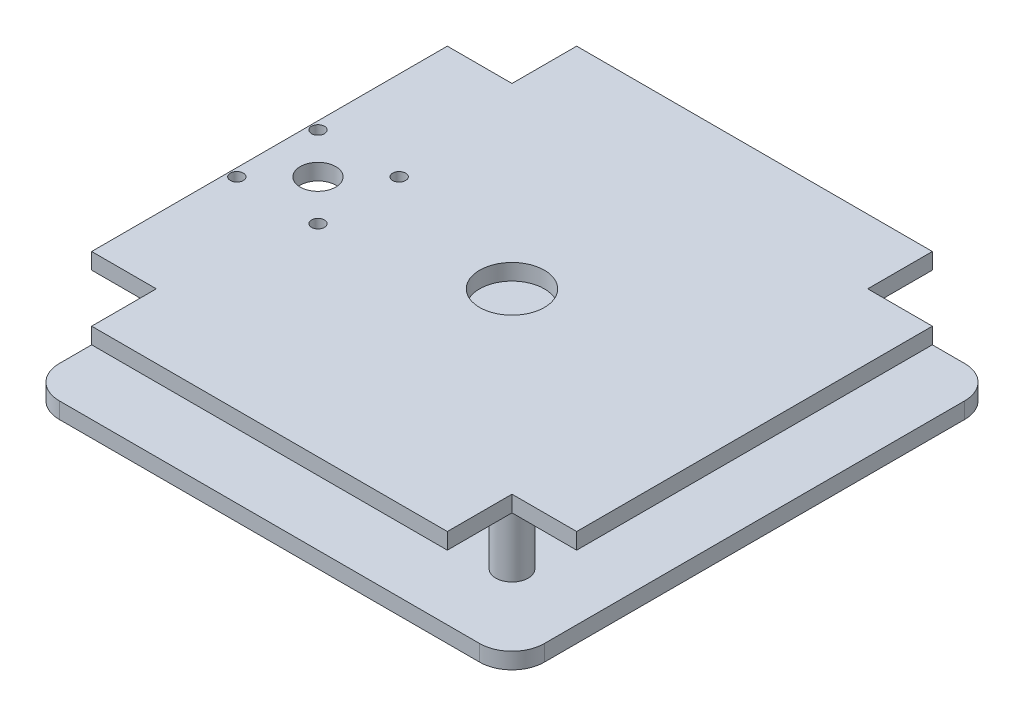
SolidWorks part; units mm, degrees
ref_plane "Front Plane" through (0, 0, 0) normal (0, 0, 1) x (1, 0, 0)
ref_plane "Top Plane" through (0, 0, 0) normal (0, 1, 0) x (1, 0, 0)
ref_plane "Right Plane" through (0, 0, 0) normal (1, 0, 0) x (0, 0, -1)
sketch "Sketch2" plane through (0, 0, 0) normal (0, 1, 0) x (1, 0, 0)
  line L1 (-75, 75) -> (75, 75)
  line L2 (-75, 75) -> (-75, -75)
  line L3 (-75, -75) -> (75, -75)
  line L4 (75, 75) -> (75, -75)
  line L5 (-75, 75) -> (75, -75) construction
  line L6 (-75, -75) -> (75, 75) construction
  point P0 (0, 0)
  dimension "D1" = 150
  dimension "D2" = 150
extrude "Boss-Extrude1" add sketch "Sketch2" along normal blind 5
sketch "Sketch3" plane through (0, 5, 0) normal (0, 1, 0) x (1, 0, 0)
  line L0 (75, -75) -> (75, 75) construction
  line L1 (75, 75) -> (-75, 75) construction
  circle A0 centre (50, 50) radius 5
  circle A2 centre (50, -50) radius 5
  circle A3 centre (-50, -50) radius 5
  circle A4 centre (-50, 50) radius 5
  point P15 (0, 0)
  dimension "D1" = 25
  dimension "D3" = 10
  dimension "D2" = 25
extrude "Boss-Extrude2" add sketch "Sketch3" along normal blind 20
sketch "Sketch4" plane through (0, 5, 0) normal (0, 1, 0) x (1, 0, 0)
  circle A0 centre (0, 0) radius 10
  dimension "D1" = 20
extrude "Cut-Extrude1" cut sketch "Sketch4" against normal through all
sketch "Sketch5" plane through (0, 5, 0) normal (0, 1, 0) x (1, 0, 0)
  circle A0 centre (-60, 0) radius 5.5
  dimension "D1" = 60
  dimension "D2" = 11
extrude "Cut-Extrude2" cut sketch "Sketch5" against normal blind 20
fillet "Fillet1" radius 10 4 edges at (-75, 2.5, 75) (75, 2.5, 75) (75, 2.5, -75) (-75, 2.5, -75)
sketch "Sketch6" plane through (0, 25, 0) normal (0, 1, 0) x (1, 0, 0)
  line L0 (-75, 65) -> (-75, -65) construction
  line L1 (-75, 65) -> (-75, -65)
  line L6 (-75, 65) -> (-75, -65)
  line L7 (-65, -75) -> (65, -75)
  line L8 (75, -65) -> (75, 65)
  line L9 (65, 75) -> (-65, 75)
  line L10 (-75, 65) -> (-75, -65)
  line L11 (-65, -75) -> (65, -75)
  line L12 (75, -65) -> (75, 65)
  line L13 (65, 75) -> (-65, 75)
  circle A2 centre (-50, 50) radius 5
  circle A3 centre (-50, 50) radius 5
  arc A7 (-75, -65) -> (-65, -75) centre (-65, -65) ccw
  arc A8 (65, -75) -> (75, -65) centre (65, -65) ccw
  arc A9 (75, 65) -> (65, 75) centre (65, 65) ccw
  arc A10 (-65, 75) -> (-75, 65) centre (-65, 65) ccw
  arc A11 (-75, -65) -> (-65, -75) centre (-65, -65) ccw
  arc A12 (65, -75) -> (75, -65) centre (65, -65) ccw
  arc A13 (75, 65) -> (65, 75) centre (65, 65) ccw
  arc A14 (-65, 75) -> (-75, 65) centre (-65, 65) ccw
  circle M10 centre (-50, 50) radius 5
  dimension "D1" = 0
  dimension "D2" = 0
extrude "Boss-Extrude3" add sketch "Sketch6" along normal blind 5 contours M10 | L13 A14 L1 A11 L11 A12 L12 A13 M10 region at (0.1758, 25, 0.1758) region at (-50, 25, -50)
sketch "Sketch8" plane through (0, 25, 0) normal (0, -1, 0) x (1, 0, 0)
  circle A0 centre (0, 0) radius 10 construction
  circle A1 centre (0, 0) radius 10
  circle A2 centre (-60, 0) radius 5.5 construction
  circle A3 centre (-60, 0) radius 5.5
extrude "Cut-Extrude3" cut sketch "Sketch8" against normal blind 5
sketch "Sketch9" plane through (0, 30, 0) normal (0, 1, 0) x (1, 0, 0)
  line L0 (-60, 0) -> (-47.4489, 12.5511) construction
  line L1 (-75, 65) -> (-75, -65) construction
  circle A0 centre (-47.4489, 12.5511) radius 2
  circle A1 centre (-60, 0) radius 5.5 construction
  circle A2 centre (-60, 0) radius 5.5
  circle A3 centre (-47.4489, -12.5511) radius 2
  circle A4 centre (-72.5511, -12.5511) radius 2
  circle A5 centre (-72.5511, 12.5511) radius 2
  point P16 (-60, 0)
  dimension "D1" = 17.75
  dimension "D2" = 4
  dimension "D3" = 45
extrude "Cut-Extrude4" cut sketch "Sketch9" against normal blind 5
sketch "Sketch10" plane through (0, 30, 0) normal (0, 1, 0) x (1, 0, 0)
  line L0 (-75, 65) -> (-75, -65) construction
  line L1 (-75, 55) -> (-55, 55)
  line L2 (-75, 55) -> (-75, 75)
  line L3 (-75, 75) -> (-55, 75)
  line L4 (-55, 55) -> (-55, 75)
  line L5 (65, 75) -> (-65, 75) construction
  line L6 (55, 75) -> (55, 55)
  line L7 (55, 75) -> (75, 75)
  line L8 (75, 75) -> (75, 55)
  line L9 (55, 55) -> (75, 55)
  line L10 (75, -55) -> (55, -55)
  line L11 (75, -55) -> (75, -75)
  line L12 (75, -75) -> (55, -75)
  line L13 (55, -55) -> (55, -75)
  line L14 (-55, -75) -> (-55, -55)
  line L15 (-55, -75) -> (-75, -75)
  line L16 (-75, -75) -> (-75, -55)
  line L17 (-55, -55) -> (-75, -55)
  point P23 (0, 0)
  dimension "D1" = 20
  dimension "D2" = 20
extrude "Cut-Extrude5" cut sketch "Sketch10" against normal blind 10
